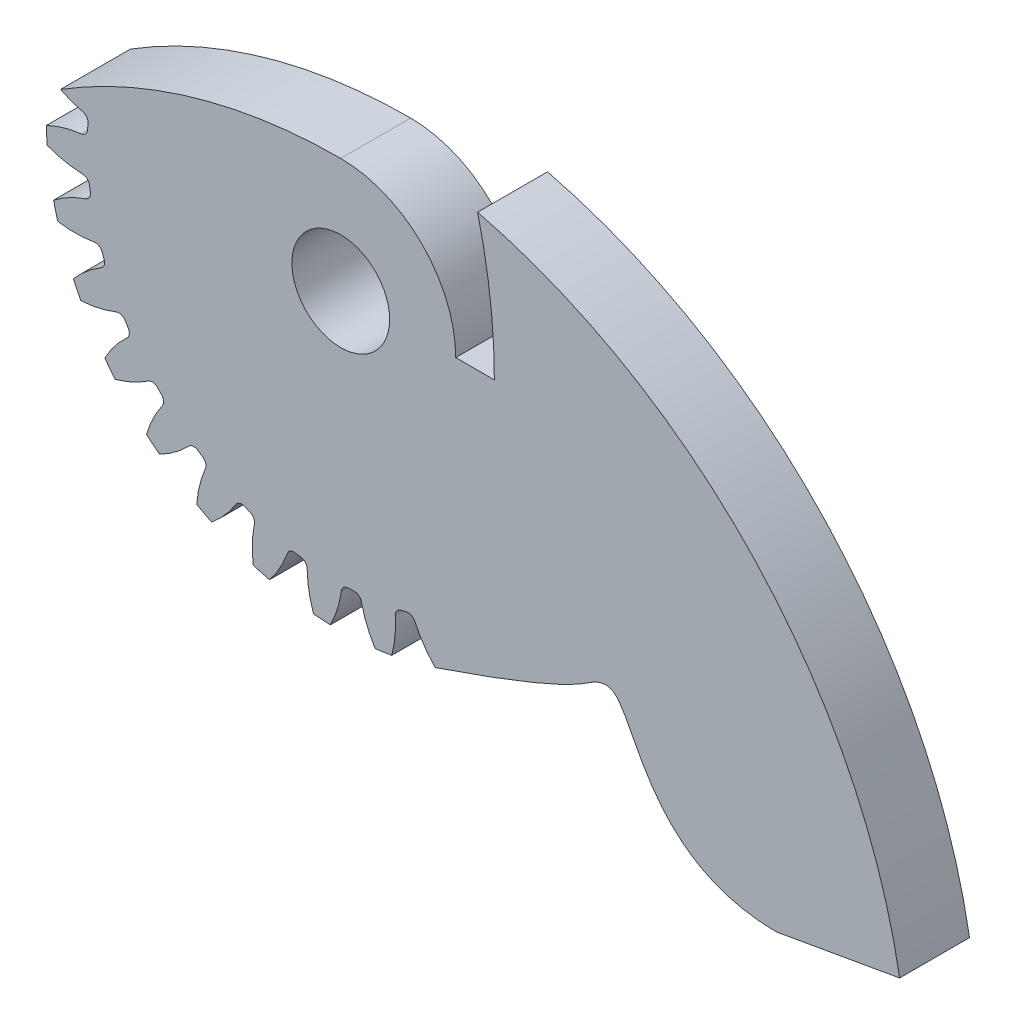
SolidWorks part; units mm, degrees
material "ABS"
ref_plane "Front" through (0, 0, 0) normal (0, 0, 1) x (1, 0, 0)
ref_plane "Top" through (0, 0, 0) normal (0, 1, 0) x (1, 0, 0)
ref_plane "Right" through (0, 0, 0) normal (1, 0, 0) x (0, 0, -1)
sketch "Sketch3" plane through (0, 0, 0) normal (0, 0, 1) x (1, 0, 0)
  circle A0 centre (0, 0) radius 40.64
  dimension "od" = 81.28
extrude "gearBody" add sketch "Sketch3" along normal blind 9.652
sketch "Sketch2" plane through (0, 0, 0) normal (0, 0, 1) x (1, 0, 0)
  line L0 (0, 0) -> (34.0786, 14.1158) construction
  line L1 (45.4751, -11.4855) -> (0, 0) construction
  line L2 (0, 0) -> (36.3143, 0) construction
  line L3 (38.0972, -0.458) -> (37.8451, -4.4001) construction
  line L5 (37.9712, -2.4291) -> (0, 0) construction
  line L7 (0, 0) -> (36.8864, 0) construction
  arc A0 (36.879, -0.7403) -> (36.6727, -3.9649) centre (0, 0) ccw construction
  arc A1 (40.637, 0.4947) -> (40.2427, -5.6687) centre (0, 0) ccw construction
  arc A2 (38.0972, -0.458) -> (37.8451, -4.4001) centre (0, 0) ccw construction
  arc A3 (34.9015, -2.6404) -> (34.9534, -1.8283) centre (0, 0) ccw
  arc A4 (45.4751, -11.4855) -> (35.6466, -3.6712) centre (32.0022, -18.3431) ccw
  arc A5 (45.4751, -11.4855) -> (46.5679, 5.5974) centre (0, 0) ccw
  arc A6 (46.5679, 5.5974) -> (35.8238, -0.9008) centre (34.0786, 14.1158) cw
  arc A7 (34.9534, -1.8283) -> (35.8238, -0.9008) centre (35.9376, -1.8798) cw
  arc A8 (35.6466, -3.6712) -> (34.9015, -2.6404) centre (35.8842, -2.7147) cw
  point P6 (46.5679, 5.5974)
  point P22 (45.4751, -11.4855)
  dimension "baseDia" = 73.7729
  dimension "od" = 81.28
  dimension "pd" = 76.2
  dimension "rd" = 70.0024
  dimension "rFillet" = 0.9855
  dimension "pointX" = 46.5679
  dimension "pointY" = 5.5974
  dimension "CTT" = 3.9421
  dimension "flankCenterAngle" = 22.5
extrude "toothCut" cut sketch "Sketch2" along normal through all
pattern_circular "CirPattern1" count 30 over 360 about axis through (0, 0, 9.652) along (0, 0, -1) of "toothCut"
sketch "hub1Dia" plane through (0, 0, 0) normal (0, 0, -1) x (-1, 0, 0)
  circle A0 centre (0, 0) radius 12.7
  dimension "hub1Dia" = 25.4
sketch "hub2Dia" plane through (0, 0, 9.652) normal (0, 0, 1) x (1, 0, 0)
  circle A0 centre (0, 0) radius 12.7
  dimension "hub2dia" = 25.4
sketch "boreDia" plane through (0, 0, 0) normal (0, 0, 1) x (1, 0, 0)
  circle A0 centre (0, 0) radius 6.7469
  dimension "boreDia" = 13.4937
extrude "bore" cut sketch "boreDia" against normal mid plane 25400
sketch "Sketch4" plane through (0, 0, 9.652) normal (0, 0, 1) x (1, 0, 0)
  circle A0 centre (0, -57.15) radius 78.359
  arc A2 (-42.9159, 8.4119) -> (42.9159, 8.4119) centre (0, 0) cw
  dimension "D1" = 156.718
  dimension "D2" = 57.15
extrude "Cut-Extrude1" cut sketch "Sketch4" against normal through all contours A0 region at (0, 27.8712, 9.652)
sketch "Sketch5" plane through (0, 0, 9.652) normal (0, 0, 1) x (1, 0, 0)
  line L0 (0, 21.209) -> (21.5163, 5.902)
  line L1 (21.5163, 5.902) -> (8.9608, -26.928)
  line L2 (8.9608, -26.928) -> (13.028, -38.4952)
  line L3 (0, 0) -> (0, -57.15) construction
  line L4 (0, -57.15) -> (-55.7146, -2.05) construction
  line L5 (0, -57.15) -> (67.8609, -96.3295) construction
  line L9 (0, -57.15) -> (77.1686, -43.5431) construction
  line L12 (60.232, -46.5295) -> (77.1686, -43.5431)
  line L13 (0, -57.15) -> (39.5947, -34.29) construction
  line L14 (39.5947, -34.29) -> (36.4197, -28.7907) construction
  circle A1 centre (0, -57.15) radius 78.359 construction
  arc A5 (0, 21.209) -> (77.1686, -43.5431) centre (0, -57.15) cw
  circle A6 centre (0, -57.15) radius 21.59 construction
  circle A12 centre (49.4934, -85.725) radius 40.64 construction
  spline S0 degree 3 poles (13.028, -38.4952) (34.3641, -31.2172) (33.2674, -29.3092) (40.5997, -27.9667) (42.6261, -46.4877) (60.232, -46.5295) knots 0 0 0 0 0.394503 0.494503 1 1 1 1
  point P28 (21.569, -56.1981)
  dimension "D1" = 43.18
  dimension "D3" = 81.28
  dimension "D6" = 156.718
  dimension "D2" = 120
  dimension "D4" = 57.15
  dimension "D8" = 57.15
  dimension "D7" = 60
  dimension "D9" = 45.72
  dimension "D10" = 6.35
  dimension "D5" = 80
extrude "Boss-Extrude1" add sketch "Sketch5" against normal up to surface (9.652 mm away) up to face at (6.7469, 0, 0)
sketch "Sketch6" plane through (0, 0, 9.652) normal (0, 0, 1) x (1, 0, 0)
  line L1 (-41.2993, 3.0747) -> (-43.5539, 7.9898)
  line L2 (15.875, 0) -> (21.209, 0)
  circle A0 centre (0, -57.15) radius 78.359 construction
  arc A1 (77.1686, -43.5431) -> (-36.286, 12.3011) centre (0, -57.15) ccw construction
  circle A2 centre (0, 0) radius 15.875 construction
  arc A3 (0, 15.875) -> (15.875, 0) centre (0, 0) cw
  arc A4 (18.8964, 18.8964) -> (-43.5539, 7.9898) centre (0, -57.15) ccw
  arc A5 (0, 15.875) -> (-41.2993, 3.0747) centre (0, -57.15) ccw
  circle A6 centre (0, 0) radius 21.209 construction
  circle A8 centre (-57.15, 0) radius 78.359 construction
  arc A9 (21.209, 0) -> (18.8964, 18.8964) centre (-57.15, 0) ccw
  dimension "D4" = 57.15
  dimension "D1" = 31.75
  dimension "D2" = 42.418
  dimension "D3" = 156.718
extrude "Cut-Extrude2" cut sketch "Sketch6" against normal through all
equation "\"Bodytube_OD\" = 6.17in"
equation "\"Bodytube_ID\" = 5.998in"
equation "\"Fwd_Tube_Length\" = 40in"
equation "\"Mid_Tube_Length\" = 1in"
equation "\"Aft_Section_Length\"= 39in"
equation "\"Mid_Coupler_Length\"= 13in"
equation "\"Aft_Lower_Length\"= 22in"
equation "\"AB_Coupler_OD_Length\"= 1in"
equation "\"AB_Coupling_Section_Length\"= 0.375in"
equation "\"AB_Coupler_Length\"= \"AB_Coupler_OD_Length\" + \"AB_Coupling_Section_Length\" * 2"
equation "\"Cutout_Angle\" = 80"
equation "\"AB_Paddle_Height\" = 0.375in"
equation "\"AB_Coupler_Num_Screws\"= 6"
equation "\"Num_Cutouts\" = 3"
equation "\"AB_Coupler_OD\"= 6.17in"
equation "\"AB_Coupler_ID\"= 5.75in"
equation "\"AB_Coupler_Surface_Diameter\"= 5.998in"
equation "\"AB_Coupling_Screw_Diameter\"= 0.1065in"
equation "\"AB_Central_Bushing_Length\" = .75in"
equation "\"Lead_Screw_Dist\" = 2.25in"
equation "\"Lead_Screw_Diam\" = 11mm"
equation "\"Lead_Screw_Length\" = (\"Mid_Coupler_Length\" + 2*0.375in + 2*0.5in)"
equation "\"Paddle_Pin_Offset\" = .25in"
equation "\"Paddle_Pin_Radius\" = 2.25in"
equation "\"Fwd_BKHD_From_Top\" = 18in"
equation "\"D1@Sketch4\"=\"Bodytube_OD\""
equation "\"D2@Sketch4\"=\"Paddle_Pin_Radius\""
equation "\"D3@Sketch5\"=\"Paddle_Gear_OD\""
equation "\"D4@Sketch5\"=\"Paddle_Pin_Radius\""
equation "\"Motor_OD\" = 4in"
equation "\"Aft_Upper_Length\"= \"Aft_Section_Length\" - \"Aft_Lower_Length\" - \"AB_Coupler_OD_Length\""
equation "\"Paddle_Gear_OD\" = 3.2in"
equation "\"D5@Sketch5\"=\"Cutout_Angle\""
equation "\"D6@Sketch5\"=\"Bodytube_OD\""
equation "\"D1@Sketch6\"=\"AB_Coupler_ID\"-2*\"Paddle_Pin_Radius\""
equation "\"D2@Sketch6\"=\"Bodytube_OD\"-2*\"Paddle_Pin_Radius\""
equation "\"D3@Sketch6\"=\"Bodytube_OD\""
equation "\"D4@Sketch6\"=\"Paddle_Pin_Radius\""
equation "\"D8@Sketch5\"=\"Paddle_Pin_Radius\""
equation "\"Drive_Gear_OD\" = 1.7in"
equation "\"Fin_Thickness\"= .118in"
equation "\"Guiderail_Cutout_Diameter\"= 1.5in"
equation "\"DB9_Hole_Dist\" = 25mm"
equation "\"D1@Sketch5\"=\"Drive_Gear_OD\""
